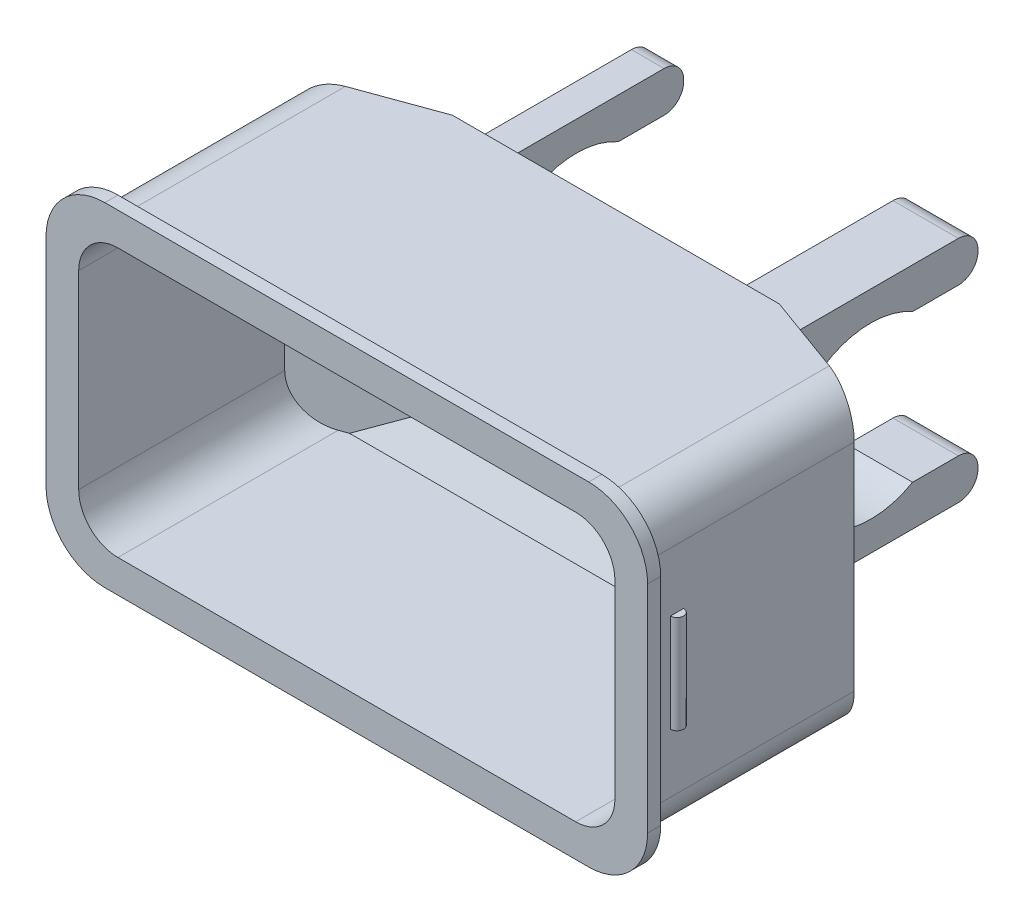
SolidWorks part; units mm, degrees
ref_plane "Front Plane" through (0, 0, 0) normal (0, 0, 1) x (1, 0, 0)
ref_plane "Top Plane" through (0, 0, 0) normal (0, 1, 0) x (1, 0, 0)
ref_plane "Right Plane" through (0, 0, 0) normal (1, 0, 0) x (0, 0, -1)
sketch "Sketch1" plane through (0, 0, 0) normal (0, 0, 1) x (1, 0, 0)
  line L0 (-41, -20.5) -> (-41, 20.5)
  line L1 (-43, -22.5) -> (43, -22.5)
  line L2 (-43, -22.5) -> (-43, 22.5)
  line L3 (-43, 22.5) -> (43, 22.5)
  line L4 (43, -22.5) -> (43, 22.5)
  line L5 (-43, -22.5) -> (43, 22.5) construction
  line L6 (-43, 22.5) -> (43, -22.5) construction
  line L7 (-41, 20.5) -> (41, 20.5)
  line L8 (41, -20.5) -> (41, 20.5)
  line L9 (-41, -20.5) -> (41, -20.5)
  point P0 (0, 0)
  dimension "D1" = 86
  dimension "D2" = 45
  dimension "D3" = 2
extrude "Boss-Extrude1" add sketch "Sketch1" against normal blind 39.15
sketch "Sketch2" plane through (0, 0, -39.15) normal (0, 0, -1) x (-1, 0, 0)
  line L8 (-43, 22.5) -> (-43, -22.5)
  line L9 (-43, -22.5) -> (43, -22.5)
  line L10 (43, -22.5) -> (43, 22.5)
  line L11 (43, 22.5) -> (-43, 22.5)
  line L12 (-43, 22.5) -> (-43, -22.5)
  line L13 (-43, -22.5) -> (43, -22.5)
  line L14 (43, -22.5) -> (43, 22.5)
  line L15 (43, 22.5) -> (-43, 22.5)
  dimension "D1" = 0
extrude "Boss-Extrude2" add sketch "Sketch2" against normal blind 2
ref_plane "Plane1" through (25, 0, 0) normal (1, 0, 0) x (0, 0, -1)
sketch "Sketch3" plane through (25, 0, 0) normal (1, 0, 0) x (0, 0, -1)
  line L0 (39.15, -22.5) -> (39.15, 22.5) construction
  line L5 (69.5273, 11.3) -> (69.5273, 17.5)
  line L6 (39.15, -17.5) -> (69.5273, -17.5)
  line L8 (59.5273, 11.3) -> (69.5273, 11.3)
  line L9 (59.5273, -11.3) -> (69.5273, -11.3)
  line L10 (39.15, 17.5) -> (69.5273, 17.5)
  line L11 (69.5273, -17.5) -> (69.5273, -11.3)
  line L12 (39.15, 17.5) -> (39.15, -17.5)
  line L14 (53.1, 0) -> (53.4242, 0.35) construction
  line L16 (39.15, 22.5) -> (0, 22.5) construction
  arc A2 (59.5273, 11.3) -> (59.5273, -11.3) centre (53.1, 0) ccw
  dimension "D2" = 13
  dimension "D1" = 13.95
  dimension "D3" = 11.3
  dimension "D4" = 11.3
  dimension "D5" = 10
  dimension "D6" = 10
  dimension "D7" = 35
  dimension "D8" = 17.5
  dimension "D9" = 22.15
extrude "Boss-Extrude3" add sketch "Sketch3" against normal blind 10
ref_plane "Plane2" through (-25, 0, 0) normal (-1, 0, 0) x (0, 0, 1)
sketch "Sketch4" plane through (-25, 0, 0) normal (-1, 0, 0) x (0, 0, 1)
  line L7 (-39.15, -17.5) -> (-39.15, 17.5)
  line L8 (-39.15, 17.5) -> (-69.5273, 17.5)
  line L9 (-69.5273, 17.5) -> (-69.5273, 11.3)
  line L10 (-69.5273, 11.3) -> (-59.5273, 11.3)
  line L11 (-59.5273, -11.3) -> (-69.5273, -11.3)
  line L12 (-69.5273, -11.3) -> (-69.5273, -17.5)
  line L13 (-69.5273, -17.5) -> (-39.15, -17.5)
  line L14 (-39.15, -17.5) -> (-39.15, 17.5)
  line L15 (-39.15, 17.5) -> (-69.5273, 17.5)
  line L16 (-69.5273, 17.5) -> (-69.5273, 11.3)
  line L17 (-69.5273, 11.3) -> (-59.5273, 11.3)
  line L18 (-59.5273, -11.3) -> (-69.5273, -11.3)
  line L19 (-69.5273, -11.3) -> (-69.5273, -17.5)
  line L20 (-69.5273, -17.5) -> (-39.15, -17.5)
  arc A1 (-59.5273, -11.3) -> (-59.5273, 11.3) centre (-53.1, 0) ccw
  arc A2 (-59.5273, -11.3) -> (-59.5273, 11.3) centre (-53.1, 0) ccw
  dimension "D1" = 0
extrude "Boss-Extrude4" add sketch "Sketch4" against normal blind 5
fillet "Fillet2" radius 3 12 edges at (-22.5, 17.5, -39.15) (-22.5, -17.5, -39.15) (20, -17.5, -39.15) (20, 17.5, -39.15) (-22.5, 17.5, -69.5273) (-22.5, 11.3, -69.5273) (-22.5, -11.3, -69.5273) (-22.5, -17.5, -69.5273) (20, -17.5, -69.5273) (20, -11.3, -69.5273) (20, 17.5, -69.5273) (20, 11.3, -69.5273)
sketch "Sketch5" plane through (0, 0, -39.15) normal (0, 0, -1) x (-1, 0, 0)
  line L2 (-43, 22.5) -> (43, 22.5) construction
  line L3 (43, -22.5) -> (-43, -22.5) construction
  line L4 (-15, 11.3) -> (-15, 14.3) construction
  line L5 (-15, 14) -> (20, 14)
  line L6 (-15, 14) -> (-15, -14)
  line L7 (-15, -14) -> (20, -14)
  line L8 (20, 14) -> (20, -14)
  line L9 (20, -20.5) -> (20, 20.5) construction
  dimension "D1" = 8.5
  dimension "D2" = 8.5
extrude "Cut-Extrude1" cut sketch "Sketch5" against normal blind 5
sketch "Sketch6" plane through (0, -20.5, 0) normal (0, 1, 0) x (1, 0, 0)
  line L1 (-41, 37.15) -> (41, 37.15) construction
  line L2 (-20, 37.15) -> (-43, 28.7787)
  line L4 (-43, 28.7787) -> (-43, 37.15)
  line L5 (-20, 37.15) -> (-43, 37.15)
  line L6 (15, 37.15) -> (43, 37.15)
  line L8 (43, 37.15) -> (43, 28.7787)
  line L9 (43, 28.7787) -> (15, 37.15)
  line L10 (-43, 39.15) -> (-43, 0) construction
  line L11 (43, 39.15) -> (43, 0) construction
  dimension "D1" = 23
  dimension "D2" = 28
  dimension "D3" = 20
extrude "Boss-Extrude5" add sketch "Sketch6" along normal up to surface (41 mm away) up to face at (0, 20.5, -18.575)
chamfer "Chamfer1" distance 5 angle 60 2 edges at (-2.5, 20.5, -37.15) (-2.5, -20.5, -37.15) first distance on face at (-0.8333, 20.5, -22.1972) first distance on face at (-0.8333, -20.5, -22.1972)
chamfer "Chamfer2" distance 18 angle 20 2 edges at (-43, 0, -39.15) (43, 0, -39.15) first distance on face at (-1.6667, 0, -39.15)
fillet "Fillet3" radius 6 8 edges at (-43, 22.5, -16.2993) (-43, -22.5, -16.2993) (43, -22.5, -16.2993) (43, 22.5, -16.2993) (-41, -20.5, -14.7533) (-41, 20.5, -14.7533) (41, 20.5, -14.6883) (41, -20.5, -14.6883)
sketch "Sketch7" plane through (0, 0, 0) normal (0, 0, 1) x (1, 0, 0)
  line L0 (37, 25.5) -> (-37, 25.5)
  line L1 (-46, 16.5) -> (-46, -16.5)
  line L2 (-37, -25.5) -> (37, -25.5)
  line L3 (46, -16.5) -> (46, 16.5)
  line L4 (37, 22.5) -> (-37, 22.5)
  line L5 (-43, 16.5) -> (-43, -16.5)
  line L6 (-37, -22.5) -> (37, -22.5)
  line L7 (43, -16.5) -> (43, 16.5)
  line L8 (37, 22.5) -> (-37, 22.5)
  line L9 (-43, 16.5) -> (-43, -16.5)
  line L10 (-37, -22.5) -> (37, -22.5)
  line L11 (43, -16.5) -> (43, 16.5)
  line L12 (-41, 14.5) -> (-41, -14.5) construction
  line L13 (-35, -20.5) -> (35, -20.5) construction
  line L14 (41, -14.5) -> (41, 14.5) construction
  line L15 (35, 20.5) -> (-35, 20.5) construction
  line L16 (-41, 14.5) -> (-41, -14.5)
  line L17 (-35, -20.5) -> (35, -20.5)
  line L18 (41, -14.5) -> (41, 14.5)
  line L19 (35, 20.5) -> (-35, 20.5)
  arc A0 (-37, 25.5) -> (-46, 16.5) centre (-37, 16.5) ccw
  arc A1 (-46, -16.5) -> (-37, -25.5) centre (-37, -16.5) ccw
  arc A2 (37, -25.5) -> (46, -16.5) centre (37, -16.5) ccw
  arc A3 (46, 16.5) -> (37, 25.5) centre (37, 16.5) ccw
  arc A4 (-37, 22.5) -> (-43, 16.5) centre (-37, 16.5) ccw
  arc A5 (-43, -16.5) -> (-37, -22.5) centre (-37, -16.5) ccw
  arc A6 (37, -22.5) -> (43, -16.5) centre (37, -16.5) ccw
  arc A7 (43, 16.5) -> (37, 22.5) centre (37, 16.5) ccw
  arc A8 (-37, 22.5) -> (-43, 16.5) centre (-37, 16.5) ccw
  arc A9 (-43, -16.5) -> (-37, -22.5) centre (-37, -16.5) ccw
  arc A10 (37, -22.5) -> (43, -16.5) centre (37, -16.5) ccw
  arc A11 (43, 16.5) -> (37, 22.5) centre (37, 16.5) ccw
  arc A12 (-35, 20.5) -> (-41, 14.5) centre (-35, 14.5) ccw construction
  arc A13 (-35, 20.5) -> (-41, 14.5) centre (-35, 14.5) ccw
  arc A14 (-41, -14.5) -> (-35, -20.5) centre (-35, -14.5) ccw construction
  arc A15 (35, -20.5) -> (41, -14.5) centre (35, -14.5) ccw construction
  arc A16 (41, 14.5) -> (35, 20.5) centre (35, 14.5) ccw construction
  arc A17 (-41, -14.5) -> (-35, -20.5) centre (-35, -14.5) ccw
  arc A18 (35, -20.5) -> (41, -14.5) centre (35, -14.5) ccw
  arc A19 (41, 14.5) -> (35, 20.5) centre (35, 14.5) ccw
  line M25 (41, 14.5) -> (41, -14.5)
  arc M26 (41, -14.5) -> (35, -20.5) centre (35, -14.5) cw
  line M27 (35, -20.5) -> (-35, -20.5)
  arc M28 (-35, -20.5) -> (-41, -14.5) centre (-35, -14.5) cw
  line M29 (-41, -14.5) -> (-41, 14.5)
  arc M30 (-41, 14.5) -> (-35, 20.5) centre (-35, 14.5) cw
  line M31 (-35, 20.5) -> (35, 20.5)
  arc M32 (35, 20.5) -> (41, 14.5) centre (35, 14.5) cw
  line M33 (37, 22.5) -> (-37, 22.5)
  arc M34 (-37, 22.5) -> (-43, 16.5) centre (-37, 16.5) ccw
  line M35 (-43, 16.5) -> (-43, -16.5)
  arc M36 (-43, -16.5) -> (-37, -22.5) centre (-37, -16.5) ccw
  line M37 (-37, -22.5) -> (37, -22.5)
  arc M38 (37, -22.5) -> (43, -16.5) centre (37, -16.5) ccw
  line M39 (43, -16.5) -> (43, 16.5)
  arc M40 (43, 16.5) -> (37, 22.5) centre (37, 16.5) ccw
  dimension "D1" = 0
  dimension "D2" = 3
extrude "Boss-Extrude6" add sketch "Sketch7" along normal blind 2 contours M40 M33 M34 M35 M36 M37 M38 M39 M32 M25 M26 M27 M28 M29 M30 M31 | L3 A3 L0 A0 L1 A1 L2 A2 M33 M40 M39 M38 M37 M36 M35 M34 region at (42.6202, 22.1202, 0) region at (40.5563, 20.0563, 0)
ref_plane "Plane3" through (0, -7.5, 0) normal (0, -1, 0) x (-1, 0, 0)
sketch "Sketch9" plane through (0, -7.5, 0) normal (0, -1, 0) x (-1, 0, 0)
  line L0 (-43, 0) -> (-43, 32.5985) construction
  line L1 (43, 32.5985) -> (43, 0) construction
  line L2 (-43, 0) -> (-43, 32.5985)
  line L3 (43, 32.5985) -> (43, 0)
  circle A0 centre (43, 5.5) radius 1
  circle A1 centre (-43, 5.5) radius 1
  dimension "D1" = 2
  dimension "D2" = 5.5
extrude "Boss-Extrude7" add sketch "Sketch9" against normal blind 15 contours L3 A0 | L2 A1 region at (43.4244, -7.5, -5.5) region at (-43.4244, -7.5, -5.5)
